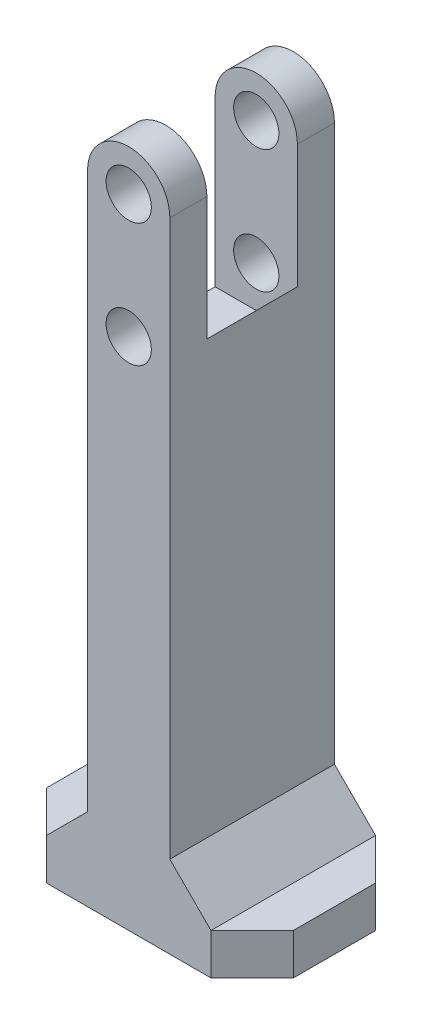
SolidWorks part; units mm, degrees
material "ABS"
ref_plane "Front Plane" through (0, 0, 0) normal (0, 0, 1) x (1, 0, 0)
ref_plane "Top Plane" through (0, 0, 0) normal (0, 1, 0) x (1, 0, 0)
ref_plane "Right Plane" through (0, 0, 0) normal (1, 0, 0) x (0, 0, -1)
ref_axis "X" through (-88.99, 0, 0) along (1, 0, 0)
ref_axis "Y" through (0, 55, 0) along (0, -1, 0)
ref_axis "Z" through (0, 0, -88.99) along (0, 0, 1)
sketch "Sketch1" plane through (0, 0, 0) normal (0, 0, 1) x (1, 0, 0)
  line L0 (0, 7.5) -> (0, -7.5) construction
  line L1 (0, -7.5) -> (0, -67.5) construction
  line L2 (5, -65) -> (5, 7.5)
  line L3 (-15, -65) -> (15, -65)
  line L4 (-15, -65) -> (-15, -70)
  line L5 (-15, -70) -> (15, -70)
  line L6 (15, -65) -> (15, -70)
  line L7 (-15, -65) -> (15, -70) construction
  line L8 (-15, -70) -> (15, -65) construction
  line L9 (-5, 7.5) -> (-5, -65)
  line L10 (0, -12.5) -> (-5, -12.5)
  arc A0 (5, 7.5) -> (-5, 7.5) centre (0, 7.5) ccw
  circle A1 centre (0, 7.5) radius 2.5 construction
  circle A2 centre (0, -7.5) radius 2.5 construction
  arc A3 (5, -7.5) -> (0, -12.5) centre (0, -7.5) cw
  point P4 (0, 0)
  dimension "D5" = 5
  dimension "D6" = 5
  dimension "D1" = 15
  dimension "D2" = 5
  dimension "D3" = 30
  dimension "D4" = 60
extrude "Boss-Extrude1" add sketch "Sketch1" along normal mid plane 20 contours L2 A0 L9 L3 | L6 L3 L4 L5 | A3 L2 A0 L9 L10 region at (0.0393, -38.4732, 0) region at (0, -67.5, 0) region at (-0.0891, -0.2611, 0)
sketch "Sketch4" plane through (0, 0, 10) normal (0, 0, 1) x (1, 0, 0)
  point P0 (0, 7.5)
  point P3 (0, -7.5)
hole_wizard "M5 Clearance Hole1" positions "Sketch4" profile "Sketch3" hole size "M5" standard "ANSI Metric" end condition through all
sketch "Sketch3" plane through (0, 7.5, 10) normal (1, 0, 0) x (0, -1, 0)
  line L0 (0, 0) -> (0, 20)
  line L1 (0, 20) -> (2.75, 20)
  line L2 (2.75, 20) -> (2.75, 0)
  line L5 (2.75, 0) -> (0, 0)
  line L11 (0, -6.35) -> (0, 107.95) construction
  dimension "Thru Hole Dia." = 5.5
  dimension "Thru Hole Depth" = 20
extrude "Cut-Extrude1" cut sketch "Sketch1<3>" against normal mid plane 11 contours A3 L2 A0 L9 L10 region at (-0.0891, -0.2611, 0)
sketch "Sketch1<3>" plane through (0, 0, 0) normal (0, 0, 1) x (1, 0, 0) same geometry as "Sketch1"
chamfer "Chamfer1" distance 5 angle 45 6 edges at (15, -67.5, -10) (15, -67.5, 10) (-15, -67.5, -10) (-15, -67.5, 10) (5, -65, 0) (-5, -65, 0)
